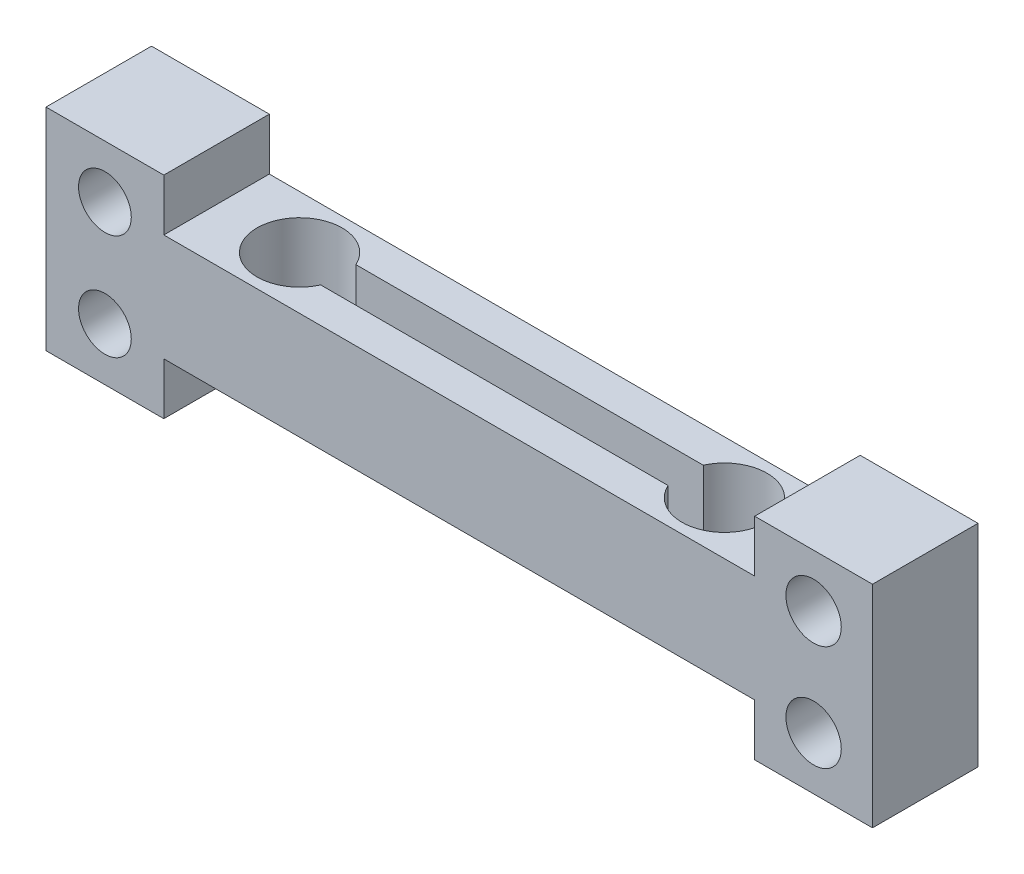
SolidWorks part; units mm, degrees
ref_plane "Front Plane" through (0, 0, 0) normal (0, 0, 1) x (1, 0, 0)
ref_plane "Top Plane" through (0, 0, 0) normal (0, 1, 0) x (1, 0, 0)
ref_plane "Right Plane" through (0, 0, 0) normal (1, 0, 0) x (0, 0, -1)
sketch "Sketch1" plane through (0, 0, 0) normal (0, 0, 1) x (1, 0, 0)
  line L0 (40.3, 3) -> (40.3, -3) construction
  line L1 (-3.35, 6) -> (3.35, 6)
  line L2 (-3.35, 6) -> (-3.35, -6)
  line L3 (-3.35, -6) -> (3.35, -6)
  line L4 (3.35, 6) -> (3.35, 3.05)
  line L5 (-3.35, 6) -> (3.35, -6) construction
  line L6 (-3.35, -6) -> (3.35, 6) construction
  line L7 (43.65, -6) -> (36.95, -6)
  line L8 (43.65, -6) -> (43.65, 6)
  line L9 (43.65, 6) -> (36.95, 6)
  line L10 (36.95, -6) -> (36.95, -3.05)
  line L11 (43.65, -6) -> (36.95, 6) construction
  line L12 (43.65, 6) -> (36.95, -6) construction
  line L13 (0, 3) -> (0, -3) construction
  line L14 (3.35, -3.05) -> (3.35, -6)
  line L15 (3.35, 3.05) -> (36.95, 3.05)
  line L17 (3.35, -3.05) -> (36.95, -3.05)
  line L19 (36.95, 3.05) -> (36.95, 6)
  line L20 (20.15, 3.05) -> (20.15, -3.05) construction
  circle A0 centre (40.3, 3) radius 1.575
  circle A1 centre (40.3, -3) radius 1.575
  circle A2 centre (0, 3) radius 1.5
  circle A3 centre (0, -3) radius 1.5
  point P0 (0, 0)
  point P6 (40.3, 0)
  point P15 (40.3, 0)
  point P17 (41.875, 3)
  point P20 (0, 0)
  point P24 (-1.5, 3)
  point P29 (20.15, 0)
  dimension "D5" = 3.15
  dimension "D6" = 6
  dimension "D7" = 3
  dimension "D8" = 6
  dimension "D1" = 12
  dimension "D2" = 6.7
  dimension "D3" = 47
  dimension "D4" = 6.7
  dimension "D9" = 6.1
extrude "Boss-Extrude1" add sketch "Sketch1" along normal mid plane 6
sketch "Sketch4" plane through (0, 0, 3) normal (0, 1, 0) x (1, 0, 0)
  line L0 (10.2737, 4) -> (30.0263, 4)
  line L1 (10.2737, 2) -> (30.0263, 2)
  line L2 (8.07, 3) -> (32.23, 3) construction
  line L3 (36.95, 0) -> (3.35, 0) construction
  arc A0 (10.2737, 4) -> (10.2737, 2) centre (8.07, 3) ccw
  arc A1 (30.0263, 2) -> (30.0263, 4) centre (32.23, 3) ccw
  point P8 (5.65, 3)
  point P9 (20.15, 3)
  point P10 (34.65, 3)
  point P11 (20.15, 0)
  dimension "D1" = 4.84
  dimension "D2" = 1
  dimension "D3" = 2
  dimension "D4" = 29
extrude "Cut-Extrude2" cut sketch "Sketch4" against normal through all both and the other way through all
